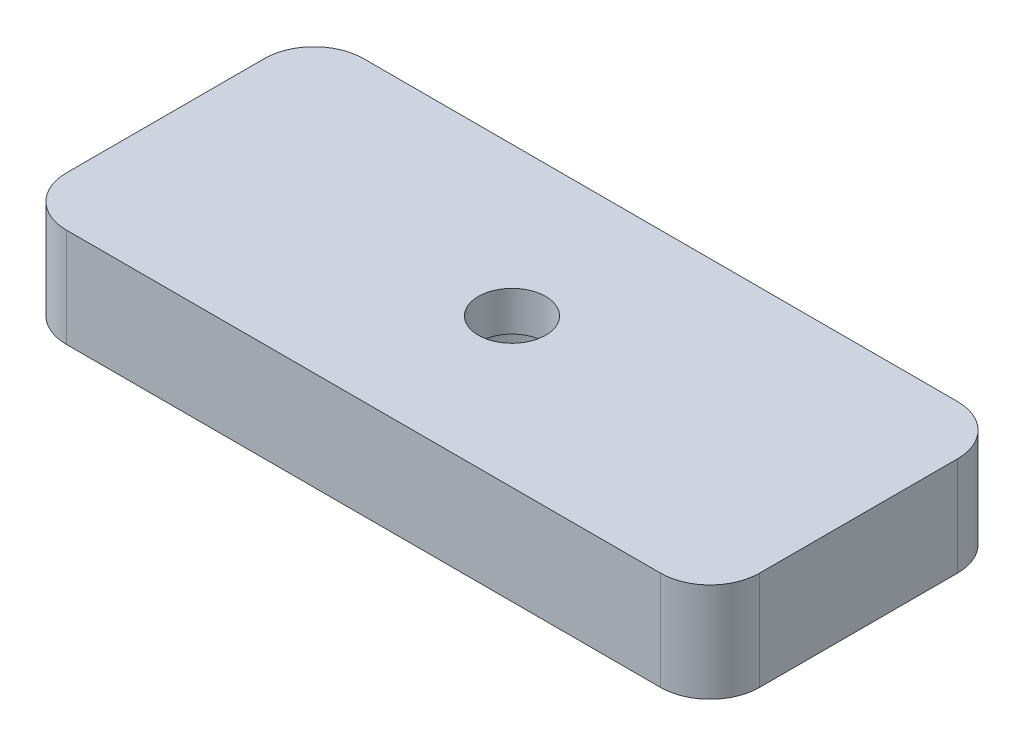
SolidWorks part; units mm, degrees
ref_plane "Front Plane" through (0, 0, 0) normal (0, 0, 1) x (1, 0, 0)
ref_plane "Top Plane" through (0, 0, 0) normal (0, 1, 0) x (1, 0, 0)
ref_plane "Right Plane" through (0, 0, 0) normal (1, 0, 0) x (0, 0, -1)
sketch "Sketch1" plane through (0, 0, 0) normal (0, 1, 0) x (1, 0, 0)
  line L1 (0, 0) -> (35, 0)
  line L2 (0, 0) -> (0, 15)
  line L3 (0, 15) -> (35, 15)
  line L4 (35, 0) -> (35, 15)
  dimension "D1" = 15
  dimension "D2" = 35
extrude "Boss-Extrude1" add sketch "Sketch1" along normal blind 5
hole_wizard "CBORE for M3 SHCS2" positions "Sketch3" profile "Sketch4" counterbore size "M3" standard "ANSI Metric" end condition through all
sketch "Sketch3" plane through (0, 0, 0) normal (0, -1, 0) x (-1, 0, 0)
  line L0 (0, 15) -> (0, 0) construction
  line L1 (0, 0) -> (-35, 0) construction
  point P0 (-17.5, 7.5)
  point P5 (0, 7.5)
  point P8 (-17.5, 0)
sketch "Sketch4" plane through (17.5, 0, -7.5) normal (1, 0, 0) x (0, 0, -1)
  line L0 (0, 0) -> (0, 5)
  line L1 (0, 5) -> (1.7, 5)
  line L3 (1.7, 5) -> (1.7, 3)
  line L4 (1.7, 3) -> (3.25, 3)
  line L5 (3.25, 3) -> (3.25, 0)
  line L7 (3.25, 0) -> (0, 0)
  line L11 (0, -6.35) -> (0, 107.95) construction
  dimension "Thru Hole Dia." = 3.4
  dimension "Thru Hole Depth" = 5
  dimension "C'Bore Dia." = 6.5
  dimension "C'Bore Depth" = 3
fillet "Fillet1" radius 2.5 4 edges at (0, 2.5, -15) (0, 2.5, 0) (35, 2.5, 0) (35, 2.5, -15)
